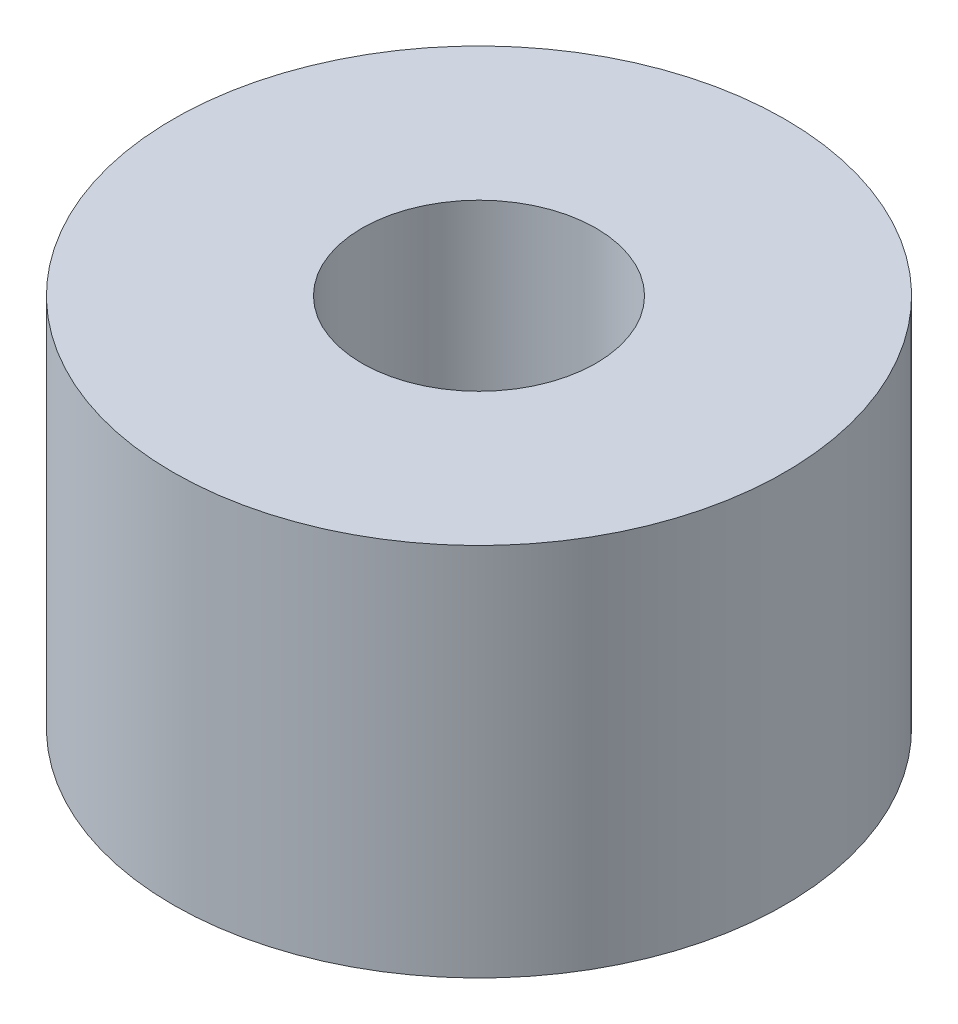
SolidWorks part; units mm, degrees
ref_plane "Front Plane" through (0, 0, 0) normal (0, 0, 1) x (1, 0, 0)
ref_plane "Top Plane" through (0, 0, 0) normal (0, 1, 0) x (1, 0, 0)
ref_plane "Right Plane" through (0, 0, 0) normal (1, 0, 0) x (0, 0, -1)
sketch "Sketch1" plane through (0, 0, 0) normal (0, 1, 0) x (1, 0, 0)
  circle A0 centre (0, 0) radius 12.446
  circle A1 centre (0, 0) radius 4.7625
  dimension "D1" = 24.892
  dimension "D2" = 9.525
extrude "Boss-Extrude1" add sketch "Sketch1" along normal blind 15.24
equation "\"OldSchoolLengthHoles\"= 2.5in'OldSchool > NewSchool"
equation "\"SchoolWidthHoles\"= 1.625in'OldSchool = NewSchool"
equation "\"Angle\"= 40deg'Looks about <= 40deg"
equation "\"Width\"= 2.125in'Pretty sure this is standardized on longboard and skateboard"
equation "\"Length\"= 3in'Will have some variation?"
equation "\"NewSchoolLengthHoles\"= 2.125in'NewSchool Mounting"
equation "\"HoleSize\"= ( 3in / 16 )'hole"
equation "\"Depth\"= 1in / 8'Assuming same depth as a riserplate"
equation "\"KingpinBoltSize\"= 3in / 8"
equation "\"PivotCupDia\"= 0.63in'0.7in (large) 0.626 (small)"
equation "\"PivotCupDepth\"= 12mm'15mm (large) 12mm (small)"
equation "\"PivotCupEndAngle\"= 21.4' Assuming it is indy pivots"
equation "\"PivotCupInnerDia\"= 0.43in'0.5in (large) 0.43 (small)"
equation "\"BushingDia\"= .98in'Bushing Diameter"
equation "\"BushingDepth\"= .6in'Bushing Depth"
equation "\"D1@Sketch1\"=\"BushingDia\""
equation "\"D2@Sketch1\"=\"KingpinBoltSize\""
equation "\"D1@Boss-Extrude1\"=\"BushingDepth\""
